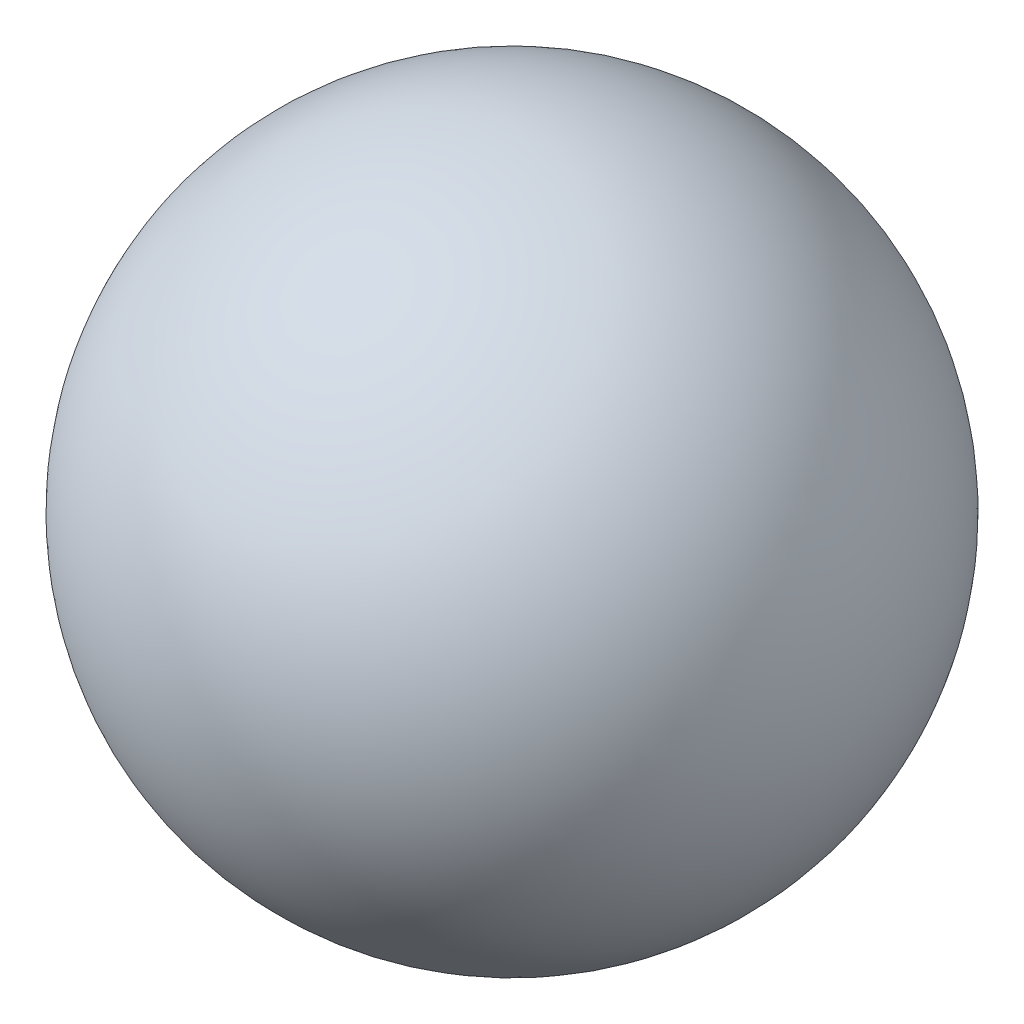
SolidWorks part; units mm, degrees
material "6061 Alloy"
ref_plane "Front Plane" through (0, 0, 0) normal (0, 0, 1) x (1, 0, 0)
ref_plane "Top Plane" through (0, 0, 0) normal (0, 1, 0) x (1, 0, 0)
ref_plane "Right Plane" through (0, 0, 0) normal (1, 0, 0) x (0, 0, -1)
sketch "Sketch1" plane through (0, 0, 0) normal (0, 1, 0) x (1, 0, 0)
  line L0 (0, 0) -> (341.122, 0) construction
  line L1 (-274.32, 0) -> (274.32, 0)
  arc A0 (274.32, 0) -> (-274.32, 0) centre (0, 0) ccw
  point P7 (341.122, 0)
  dimension "D1" = 548.64
revolve "Revolve6" add sketch "Sketch1" angle 360 about L1
shell "Shell1" thickness 3.175
sketch "Sketch2" plane through (0, 0, 0) normal (0, 1, 0) x (1, 0, 0)
  line L0 (-367.919, 0) -> (367.919, 0)
  line L1 (367.919, -152.4) -> (367.919, 152.4)
  line L2 (152.3949, -367.9211) -> (367.9211, -152.3949)
  line L3 (-152.4, -367.919) -> (152.4, -367.919)
  line L4 (-367.9211, -152.3949) -> (-152.3949, -367.9211)
  line L5 (-367.919, 152.4) -> (-367.919, -152.4)
  line L6 (-152.3949, 367.9211) -> (-367.9211, 152.3949)
  line L7 (152.4, 367.919) -> (-152.4, 367.919)
  line L8 (367.9211, 152.3949) -> (152.3949, 367.9211)
  line L9 (141.876, 342.519) -> (-141.876, 342.519)
  line L10 (-141.876, 342.519) -> (-342.519, 141.876)
  line L11 (-342.519, 141.876) -> (-342.519, -141.876)
  line L12 (-342.519, -141.876) -> (-141.876, -342.519)
  line L13 (-141.876, -342.519) -> (141.876, -342.519)
  line L14 (141.876, -342.519) -> (342.519, -141.876)
  line L15 (342.519, -141.876) -> (342.519, 141.876)
  line L16 (342.519, 141.876) -> (141.876, 342.519)
  line L17 (-342.519, 152.4) -> (-342.519, -152.4) construction
  line L18 (-134.4344, 349.9606) -> (-349.9606, 134.4344) construction
  line L19 (152.4, 342.519) -> (-152.4, 342.519) construction
  line L20 (349.9606, 134.4344) -> (134.4344, 349.9606) construction
  line L21 (342.519, -152.4) -> (342.519, 152.4) construction
  line L22 (134.4344, -349.9606) -> (349.9606, -134.4344) construction
  line L23 (-152.4, -342.519) -> (152.4, -342.519) construction
  line L24 (-349.9606, -134.4344) -> (-134.4344, -349.9606) construction
  point P4 (0, 0)
  point P7 (367.919, 0)
  point P8 (0, 0)
  point P9 (0, 0)
  dimension "D1" = 735.838
  dimension "D2" = 304.8
  dimension "D4" = 25.4
  dimension "D3" = 8
sketch "Sketch3" plane through (0, 0, 0) normal (0, 0, 1) x (1, 0, 0)
  line L0 (0, 0) -> (0, -356.8956) construction
ref_plane "Plane2" through (0, 0, 0) normal (-0.7071, 0, 0.7071) x (0, -1, 0)
sketch3d "3DSketch1"
  line L0 (342.519, 0, -141.876) -> (274.3124, 0, 0) construction
  line L1 (-367.919, 0, 0) -> (367.919, 0, 0) construction
  line L2 (342.519, 0, -141.876) -> (342.519, -330.2, -141.876) construction
  line L3 (274.3124, 0, 0) -> (342.519, -330.2, -141.876)
  line L4 (274.3124, 0, 0) -> (342.519, -330.2, 141.876)
  line L5 (-274.3124, 0, 0) -> (-342.519, -330.2, 141.876)
  line L6 (-274.3124, 0, 0) -> (-342.519, -330.2, -141.876)
  line L7 (0, 0, 274.3124) -> (141.876, -330.2, 342.519)
  line L8 (0, 0, 274.3124) -> (-141.876, -330.2, 342.519)
  line L9 (0, 0, -274.3124) -> (-141.876, -330.2, -342.519)
  line L10 (0, 0, -274.3124) -> (141.876, -330.2, -342.519)
  dimension "D1" = 68.2066
  dimension "D2" = 330.2
